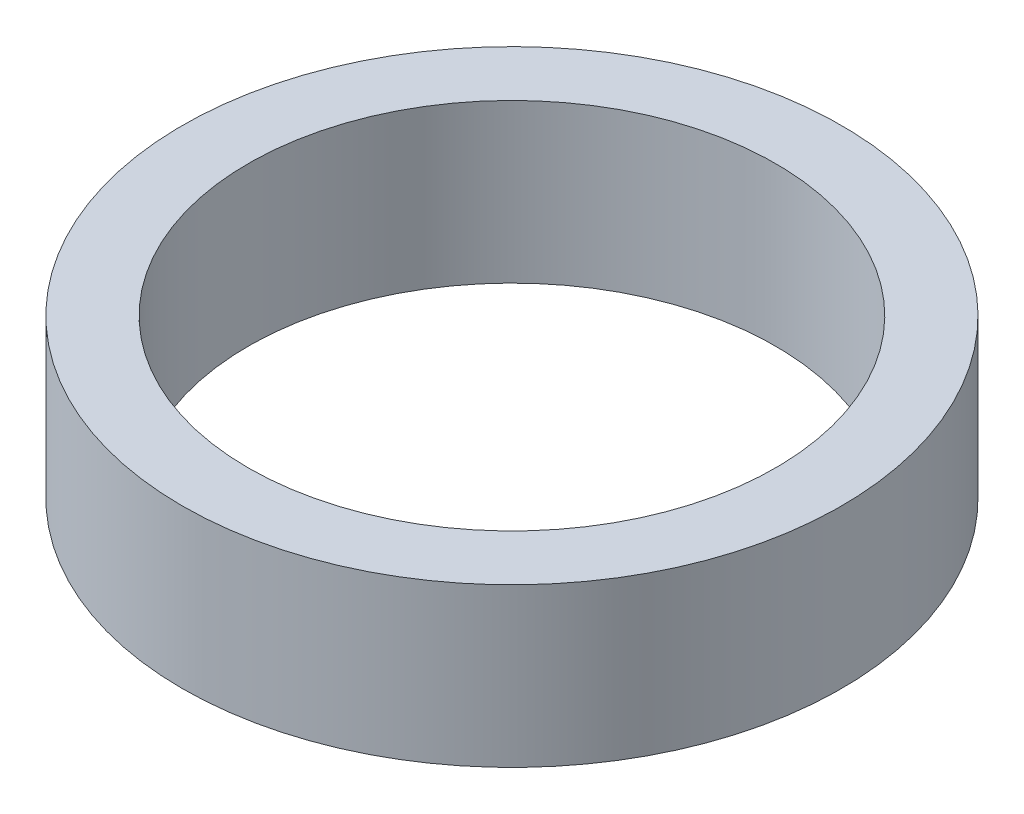
SolidWorks part; units mm, degrees
ref_plane "Front Plane" through (0, 0, 0) normal (0, 0, 1) x (1, 0, 0)
ref_plane "Top Plane" through (0, 0, 0) normal (0, 1, 0) x (1, 0, 0)
ref_plane "Right Plane" through (0, 0, 0) normal (1, 0, 0) x (0, 0, -1)
sketch "Sketch1" plane through (0, 0, 0) normal (0, 1, 0) x (1, 0, 0)
  circle A0 centre (0, 0) radius 50
  dimension "FLANGE_OD" = 100
extrude "Boss-Extrude1" add sketch "Sketch1" along normal blind 24
sketch "Sketch2" plane through (0, 0, 0) normal (0, 1, 0) x (1, 0, 0)
  circle A0 centre (0, 0) radius 40
  dimension "BORE_D" = 80
extrude "Cut-Extrude1" cut sketch "Sketch2" along normal through all
sketch "Sketch3" plane through (0, 24, 0) normal (0, 1, 0) x (1, 0, 0)
  circle A0 centre (0, 0) radius 22.2915 construction
  circle A1 centre (-22.2915, 0) radius 1.5288
  dimension "BOLT_D" = 3.0575
  dimension "BOLT_PCD" = 44.5831
extrude "Cut-Extrude2" cut sketch "Sketch3" against normal blind 22.3532 rebuild error yes
pattern_circular "CirPattern1" count 4 over 360 rebuild error yes
